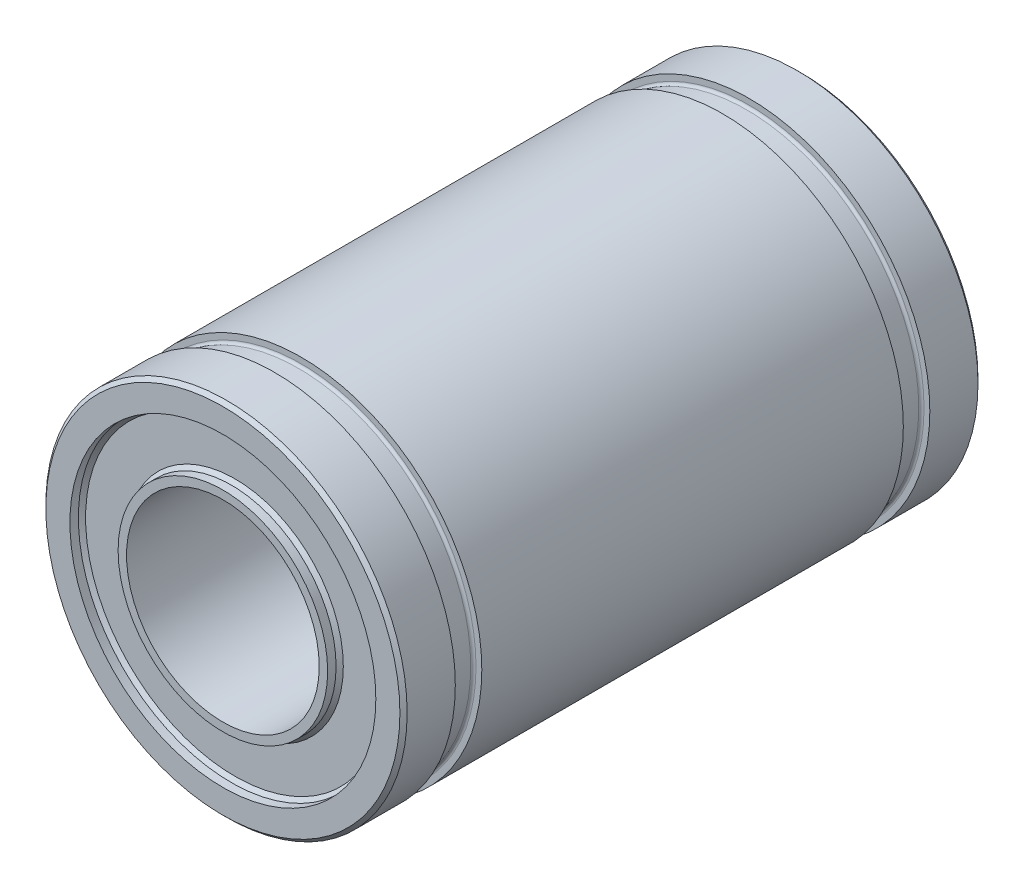
SolidWorks part; units mm, degrees
note: '?' marks a value the reader was unsure of.
material "1060 Alloy"
ref_plane "Front Plane" through (0, 0, 0) normal (0, 0, 1) x (1, 0, 0)
ref_plane "Top Plane" through (0, 0, 0) normal (0, 1, 0) x (1, 0, 0)
ref_plane "Right Plane" through (0, 0, 0) normal (1, 0, 0) x (0, 0, -1)
sketch "Sketch1" plane through (0, 0, 0) normal (0, 0, 1) x (1, 0, 0)
  circle A0 centre (0, 0) radius 7.5
  circle A1 centre (0, 0) radius 4
  dimension "D1" = 8
  dimension "D2" = 15
extrude "Boss-Extrude1" add sketch "Sketch1" against normal blind 24
sketch "Sketch2" plane through (0, 0, 0) normal (0, 0, 1) x (1, 0, 0)
  circle A0 centre (0, 0) radius 6.35
  circle A1 centre (0, 0) radius 4.35
  dimension "D1" = 12.7
  dimension "D2" = 8.7
extrude "Cut-Extrude1" cut sketch "Sketch2" against normal blind 0.5
sketch "Sketch3" plane through (0, 0, -24) normal (0, 0, -1) x (-1, 0, 0)
  circle A0 centre (0, 0) radius 6.35
  circle A1 centre (0, 0) radius 4.35
  dimension "D1" = 8.7
  dimension "D2" = 12.7
extrude "Cut-Extrude2" cut sketch "Sketch3" against normal blind 0.5
sketch3d "3DSketch1"
  point P0 (7.2089, 2.0693, -16.8167)
ref_axis "Axis1" through (0, 0, -24) along (0, 0, 1)?
ref_plane "Plane5" through (0, 0, 0) normal (-0.2759, 0.9612, 0) x (-0.9297, -0.2669, 0.2538)
sketch "Groove Sketch" plane through (10.524, 3.0208, -25.3152) normal (-0.2759, 0.9612, 0) x (-0.244, -0.07, -0.9673)
  line L0 (-16.7211, 23.213) -> (-16.6602, 23.4451)
  line L1 (-16.6602, 23.4451) -> (-17.7242, 23.7243)
  line L2 (-17.7242, 23.7243) -> (-17.7851, 23.4922)
  line L3 (-17.7066, 23.3579) -> (-16.8555, 23.1345)
  line L4 (15.0734, 7.3645) -> (-9.4759, 13.8061) construction
  line L6 (1.5068, 10.9243) -> (-21.7073, 17.0156) construction
  line L7 (-19.8038, 24.27) -> (-23.6109, 9.7612) construction
  arc A0 (-16.8555, 23.1345) -> (-16.7211, 23.213) centre (-16.8275, 23.2409) ccw
  arc A1 (-17.7066, 23.3579) -> (-17.7851, 23.4922) centre (-17.6787, 23.4643) cw
  point P10 (-17.281, 23.2462)
  dimension "Radius" = 0.11
  dimension "ID" = 14.3
  dimension "OD" = 15
  dimension "Width" = 1.1
  dimension "D1" = 3.25
revolve "Retaining Ring Groove" cut sketch "Groove Sketch" angle 360 about L4 reverse direction yes
other "shaft circlip - normal<1>"
sketch3d "3DSketch11"
  point P0 (7.2089, 2.0693, -16.8167)
ref_axis "Axis11" through (0, 0, -24) along (0, 0, 1)?
ref_plane "Plane51" through (0, 0, 0) normal (-0.2759, 0.9612, 0) x (-0.9297, -0.2669, 0.2538)
sketch "Groove Sketch1" plane through (10.524, 3.0208, -25.3152) normal (-0.2759, 0.9612, 0) x (-0.244, -0.07, -0.9673)
  line L0 (1.2698, 18.4922) -> (1.3307, 18.7244)
  line L1 (1.3307, 18.7244) -> (0.2668, 19.0036)
  line L2 (0.2668, 19.0036) -> (0.2058, 18.7714)
  line L3 (0.2843, 18.6371) -> (1.1355, 18.4138)
  line L4 (15.0734, 7.3645) -> (-9.4759, 13.8061) construction
  line L6 (1.5068, 10.9243) -> (-18.5638, 16.1907) construction
  line L7 (-0.3967, 3.6699) -> (3.4103, 18.1787) construction
  arc A0 (1.1355, 18.4138) -> (1.2698, 18.4922) centre (1.1634, 18.5202) ccw
  arc A1 (0.2843, 18.6371) -> (0.2058, 18.7714) centre (0.3122, 18.7435) cw
  point P10 (0.7099, 18.5254)
  dimension "Radius" = 0.11
  dimension "ID" = 14.3
  dimension "OD" = 15
  dimension "Width" = 1.1
  dimension "D1" = 3.25
revolve "Retaining Ring Groove1" cut sketch "Groove Sketch1" angle 360 about L4 reverse direction yes
other "shaft circlip - normal<2>"
chamfer "Chamfer1" distance 0.15 angle 45 6 edges at (-6.35, 0, -23.5) (-4.35, 0, -23.5) (6.35, 0, -0.5) (4.35, 0, -0.5) (7.5, 0, -24) (7.5, 0, 0)
